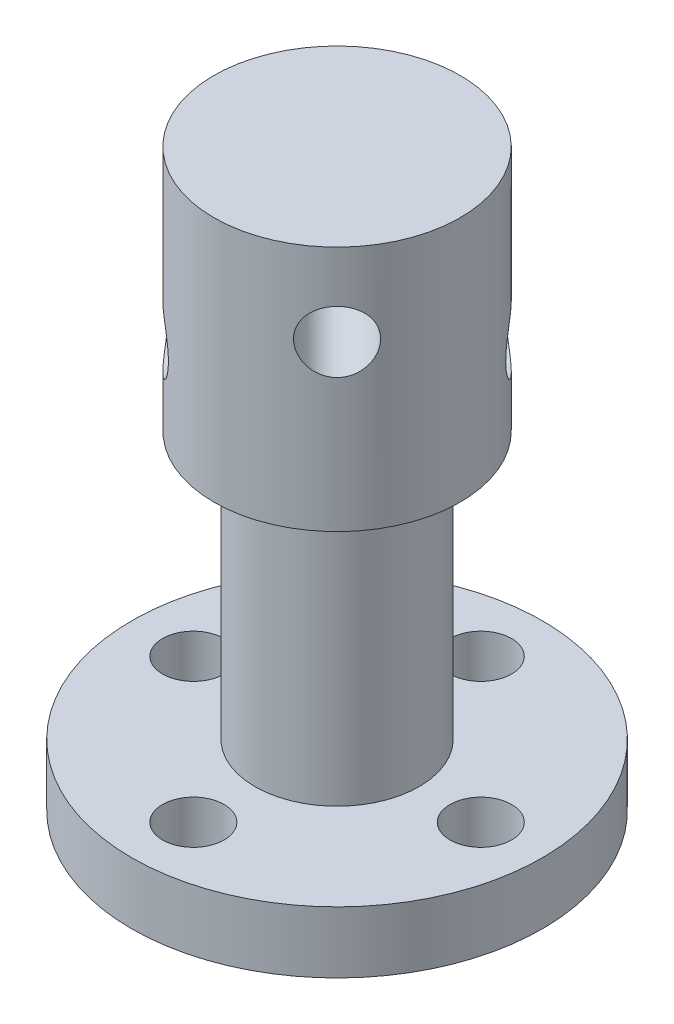
SolidWorks part; units mm, degrees
ref_plane "前视基准面" through (0, 0, 0) normal (0, 0, 1) x (1, 0, 0)
ref_plane "上视基准面" through (0, 0, 0) normal (0, 1, 0) x (1, 0, 0)
ref_plane "右视基准面" through (0, 0, 0) normal (1, 0, 0) x (0, 0, -1)
sketch "草图1" plane through (0, 0, 0) normal (0, 1, 0) x (1, 0, 0)
  line L0 (0, 0) -> (0, 7) construction
  circle A0 centre (0, 0) radius 10
  circle A1 centre (0, 0) radius 3
  circle A2 centre (0, 7) radius 1.5
  circle A3 centre (7, 0) radius 1.5
  circle A4 centre (0, -7) radius 1.5
  circle A5 centre (-7, 0) radius 1.5
  dimension "D1" = 4
extrude "凸台-拉伸1" add sketch "草图1" along normal blind 3
sketch "草图2" plane through (0, 0, 0) normal (0, 1, 0) x (1, 0, 0)
  circle A0 centre (0, 0) radius 4
extrude "凸台-拉伸2" add sketch "草图2" along normal blind 16
sketch "草图3" plane through (0, 0, 0) normal (0, 0, 1) x (1, 0, 0)
  line L0 (0, 0) -> (0, 12.3304) construction
ref_axis "基准轴1" through (0, 0, 0) along (0, 1, 0)
ref_plane "基准面1" through (0, 0, 0) normal (0.7071, 0, -0.7071) x (0, 1, 0)
sketch "草图5" plane through (0, 0, 0) normal (0.7071, 0, -0.7071) x (0, 1, 0)
  line L0 (16, 0) -> (20, 0) construction
  line L1 (16, -4) -> (16, 4) construction
  line L2 (0, 0) -> (12.3304, 0) construction
  circle A0 centre (20, 0) radius 1.5
sketch "草图6" plane through (0, 16, 0) normal (0, 1, 0) x (1, 0, 0)
  circle A0 centre (0, 0) radius 6
extrude "凸台-拉伸3" add sketch "草图6" along normal blind 12
extrude "切除-拉伸1" cut sketch "草图5" against normal through all both and the other way through all
ref_plane "基准面10" through (0, 0, 0) normal (-0.7071, 0, -0.7071) x (0, 1, 0)
sketch "草图7" plane through (0, 0, 0) normal (-0.7071, 0, -0.7071) x (0, 1, 0)
  line L0 (0, 0) -> (24, 0) construction
  line L1 (12.5209, 0) -> (-12.5209, 0) construction
  circle A0 centre (24, 0) radius 1.5
extrude "切除-拉伸3" cut sketch "草图7" against normal through all both and the other way through all
